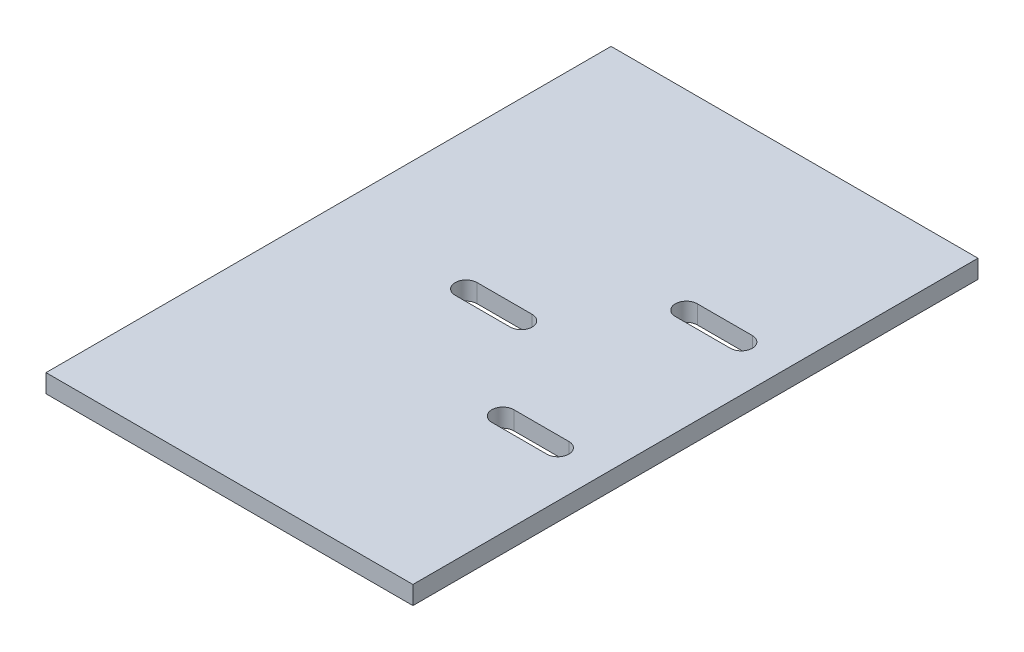
SolidWorks part; units mm, degrees
ref_plane "Front Plane" through (0, 0, 0) normal (0, 0, 1) x (1, 0, 0)
ref_plane "Top Plane" through (0, 0, 0) normal (0, 1, 0) x (1, 0, 0)
ref_plane "Right Plane" through (0, 0, 0) normal (1, 0, 0) x (0, 0, -1)
sketch "Sketch1" plane through (0, 0, 0) normal (0, 1, 0) x (1, 0, 0)
  line L0 (73.3491, 51.6462) -> (19.3491, 51.6462) construction
  line L1 (-26.6509, 128.6462) -> (73.3491, 128.6462)
  line L2 (-26.6509, 128.6462) -> (-26.6509, -25.3538)
  line L3 (-26.6509, -25.3538) -> (73.3491, -25.3538)
  line L4 (73.3491, 128.6462) -> (73.3491, -25.3538)
  line L5 (7.3491, 51.6462) -> (-26.6509, 51.6462) construction
  line L6 (73.3491, 51.6462) -> (-26.6509, 51.6462) construction
  line L7 (45.8491, 76.6462) -> (60.8491, 76.6462) construction
  line L8 (45.8491, 79.6462) -> (60.8491, 79.6462)
  line L9 (45.8491, 73.6462) -> (60.8491, 73.6462)
  line L10 (10.8491, 51.6462) -> (25.8491, 51.6462) construction
  line L11 (10.8491, 54.6462) -> (25.8491, 54.6462)
  line L12 (10.8491, 48.6462) -> (25.8491, 48.6462)
  line L13 (45.8491, 26.6462) -> (60.8491, 26.6462) construction
  line L14 (45.8491, 29.6462) -> (60.8491, 29.6462)
  line L15 (45.8491, 23.6462) -> (60.8491, 23.6462)
  circle A2 centre (18.3491, 51.6462) radius 3 construction
  circle A3 centre (53.3491, 76.6462) radius 3 construction
  circle A4 centre (53.3491, 26.6462) radius 3 construction
  arc A5 (45.8491, 79.6462) -> (45.8491, 73.6462) centre (45.8491, 76.6462) ccw
  arc A6 (60.8491, 73.6462) -> (60.8491, 79.6462) centre (60.8491, 76.6462) ccw
  arc A7 (10.8491, 54.6462) -> (10.8491, 48.6462) centre (10.8491, 51.6462) ccw
  arc A8 (25.8491, 48.6462) -> (25.8491, 54.6462) centre (25.8491, 51.6462) ccw
  arc A9 (45.8491, 29.6462) -> (45.8491, 23.6462) centre (45.8491, 26.6462) ccw
  arc A10 (60.8491, 23.6462) -> (60.8491, 29.6462) centre (60.8491, 26.6462) ccw
  point P16 (53.3491, 76.6462)
  point P23 (18.3491, 51.6462)
  point P30 (53.3491, 26.6462)
  point P35 (0, 0)
  point P36 (0, 0)
  point P37 (0, 0)
  point P38 (0, 0)
  point P39 (0, 0)
  dimension "D3" = 6
  dimension "D4" = 6
  dimension "D9" = 3
  dimension "D11" = 3
  dimension "D13" = 3
  dimension "D1" = 154
  dimension "D2" = 100
  dimension "D5" = 55
  dimension "D6" = 20
  dimension "D7" = 25
  dimension "D8" = 15
  dimension "D10" = 15
  dimension "D12" = 15
extrude "Boss-Extrude1" add sketch "Sketch1" along normal blind 5
